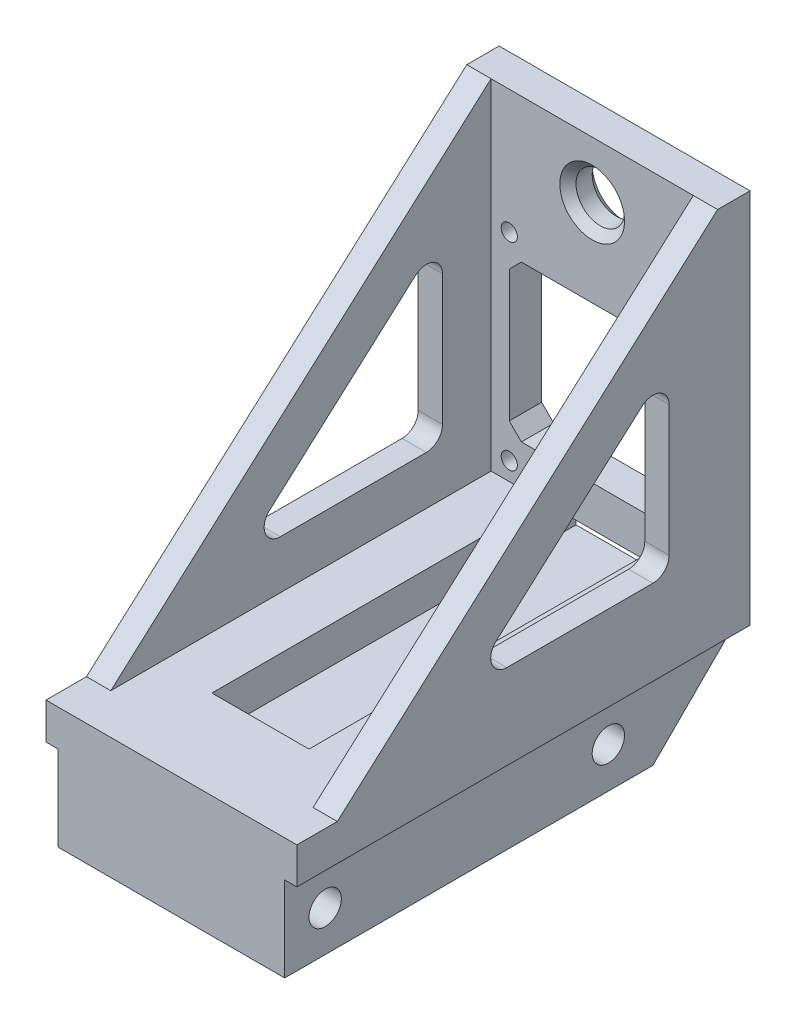
SolidWorks part; units mm, degrees
ref_plane "Front Plane" through (0, 0, 0) normal (0, 0, 1) x (1, 0, 0)
ref_plane "Top Plane" through (0, 0, 0) normal (0, 1, 0) x (1, 0, 0)
ref_plane "Right Plane" through (0, 0, 0) normal (1, 0, 0) x (0, 0, -1)
sketch "Sketch2" plane through (0, 0, 0) normal (0, 0, 1) x (1, 0, 0)
  line L1 (-12.5, -21) -> (12.5, -21)
  line L2 (-12.5, -21) -> (-12.5, 21)
  line L3 (-12.5, 21) -> (12.5, 21)
  line L4 (12.5, -21) -> (12.5, 21)
  line L5 (-12.5, -21) -> (12.5, 21) construction
  line L6 (-12.5, 21) -> (12.5, -21) construction
  point P0 (0, 0)
  dimension "D1" = 25
  dimension "D2" = 42
extrude "Boss-Extrude1" add sketch "Sketch2" along normal blind 4
sketch "Sketch5" plane through (12.5, 0, 0) normal (1, 0, 0) x (0, 0, -1)
  line L0 (-4, -21) -> (-4, 21) construction
  line L1 (0, -21) -> (-56, -21)
  line L2 (0, -21) -> (0, -36)
  line L3 (0, -36) -> (-56, -36)
  line L4 (-56, -21) -> (-56, -36)
  dimension "D1" = 15
  dimension "D2" = 52
extrude "Boss-Extrude2" add sketch "Sketch5" against normal through all
sketch "Sketch6" plane through (12.5, 0, 0) normal (1, 0, 0) x (0, 0, -1)
  line L1 (-4, 21) -> (0, 21)
  line L2 (0, 21) -> (0, -36)
  line L3 (0, -36) -> (-56, -36)
  line L4 (-56, -36) -> (-56, -21)
  line L5 (-56, -21) -> (-51, -21)
  line L6 (-4, -21) -> (-56, -21) construction
  line L7 (-51, -21) -> (-4, 21)
  dimension "D1" = 5
extrude "Boss-Extrude3" add sketch "Sketch6" along normal blind 3
sketch "Sketch7" plane through (0, 0, 56) normal (0, 0, 1) x (1, 0, 0)
  line L1 (15.5, -36) -> (14, -36)
  line L2 (15.5, -36) -> (15.5, -25.5)
  line L3 (15.5, -25.5) -> (14, -25.5)
  line L4 (14, -36) -> (14, -25.5)
  dimension "D1" = 10.5
  dimension "D2" = 1.5
extrude "Cut-Extrude1" cut sketch "Sketch7" against normal through all
sketch "Sketch9" plane through (14, 0, 0) normal (1, 0, 0) x (0, 0, -1)
  line L0 (-56, -25.5) -> (-56, -36) construction
  line L1 (0, -36) -> (-56, -36) construction
  circle A0 centre (-51, -31) radius 2
  circle A1 centre (-16, -31) radius 2
  point P5 (0, 0)
  point P9 (0, 0)
  dimension "D1" = 5
  dimension "D2" = 35
  dimension "D3" = 4
  dimension "D4" = 5
extrude "Cut-Extrude2" cut sketch "Sketch9" against normal blind 6
mirror "Mirror1" about plane through (0, 0, 0) normal (1, 0, 0) of "Cut-Extrude2", "Cut-Extrude1", "Boss-Extrude3"
chamfer "Chamfer1" distance 10.5 angle 45 1 edges at (0, -36, 0)
sketch "Sketch10" plane through (0, 0, 4) normal (0, 0, 1) x (1, 0, 0)
  line L0 (-12.5, -21) -> (12.5, -21) construction
  line L1 (-10.25, -18.75) -> (10.25, -18.75) construction
  line L2 (-10.25, -18.75) -> (-10.25, 5.7) construction
  line L3 (-10.25, 5.7) -> (10.25, 5.7) construction
  line L4 (10.25, -18.75) -> (10.25, 5.7) construction
  line L5 (-10.25, -18.75) -> (10.25, 5.7) construction
  line L6 (-10.25, 5.7) -> (10.25, -18.75) construction
  circle A0 centre (-10.25, 5.7) radius 1
  circle A1 centre (10.25, 5.7) radius 1
  circle A2 centre (10.25, -18.75) radius 1
  circle A3 centre (-10.25, -18.75) radius 1
  point P0 (0, -6.525)
  dimension "D4" = 2
  dimension "D1" = 24.45
  dimension "D2" = 20.5
  dimension "D3" = 2.25
extrude "Cut-Extrude3" cut sketch "Sketch10" against normal through all
sketch "Sketch11" plane through (0, 0, 4) normal (0, 0, 1) x (1, 0, 0)
  line L1 (-10.25, -16) -> (10.25, -16)
  line L2 (-10.25, -16) -> (-10.25, 3.25)
  line L3 (-10.25, 3.25) -> (10.25, 3.25)
  line L4 (10.25, -16) -> (10.25, 3.25)
  line L5 (-10.25, -16) -> (10.25, 3.25) construction
  line L6 (-10.25, 3.25) -> (10.25, -16) construction
  circle A1 centre (-10.25, -18.75) radius 1 construction
  point P0 (0, -6.375)
  dimension "D1" = 20.5
  dimension "D2" = 19.25
  dimension "D3" = 2.75
extrude "Cut-Extrude4" cut sketch "Sketch11" against normal through all
chamfer "Chamfer3" distance 1.5 angle 45 4 edges at (10.25, -16, 2) (-10.25, -16, 2) (-10.25, 3.25, 2) (10.25, 3.25, 2)
sketch "Sketch12" plane through (0, 0, 4) normal (0, 0, 1) x (1, 0, 0)
  line L0 (8.75, 3.25) -> (-8.75, 3.25) construction
  circle A0 centre (0, 14) radius 3
  dimension "D1" = 6
  dimension "D2" = 10.75
extrude "Cut-Extrude5" cut sketch "Sketch12" against normal through all
chamfer "Chamfer4" distance 1 angle 45 2 edges at (3, 14, 4) (3, 14, 0)
sketch "Sketch13" plane through (0, 0, 0) normal (0, 0, -1) x (-1, 0, 0)
  circle A0 centre (-10.25, 5.7) radius 2
  circle A1 centre (10.25, 5.7) radius 2
  circle A2 centre (10.25, -18.75) radius 2
  circle A3 centre (-10.25, -18.75) radius 2
  dimension "D1" = 4
extrude "Cut-Extrude6" cut sketch "Sketch13" against normal blind 1.5
sketch "Sketch14" plane through (-12.5, 0, 0) normal (1, 0, 0) x (0, 0, -1)
  line L6 (-35.2812, -15) -> (-10, -15)
  line L7 (-10, -15) -> (-10, 7.5917)
  line L8 (-10, 7.5917) -> (-35.2812, -15)
  line L9 (-35.2812, -15) -> (-10, -15)
  line L10 (-10, -15) -> (-10, 7.5917)
  line L12 (-10, 7.5917) -> (-35.2812, -15)
  dimension "D1" = 6
extrude "Cut-Extrude7" cut sketch "Sketch14" against normal through all
mirror "Mirror2" about plane through (0, 0, 0) normal (1, 0, 0) of "Cut-Extrude7"
fillet "Fillet1" radius 2 6 edges at (-14, -15, 35.2812) (-14, 7.5917, 10) (-14, -15, 10) (14, -15, 10) (14, -15, 35.2812) (14, 7.5917, 10)
sketch "Sketch16" plane through (0, -21, 0) normal (0, 1, 0) x (1, 0, 0)
  line L0 (15.5, 0) -> (-15.5, 0) construction
  line L1 (-6, -45) -> (6, -45)
  line L2 (-6, -45) -> (-6, 0)
  line L3 (-6, 0) -> (6, 0)
  line L4 (6, -45) -> (6, 0)
  line L5 (-6, -45) -> (6, 0) construction
  line L6 (-6, 0) -> (6, -45) construction
  point P0 (0, -22.5)
  point P7 (0, 0)
  dimension "D1" = 45
  dimension "D2" = 12
extrude "Cut-Extrude8" cut sketch "Sketch16" against normal up to vertex (4.5 mm away) up to point (14, -25.5, 0)
chamfer "Chamfer5" distance 4.5 angle 45 1 edges at (0, -25.5, 45)
